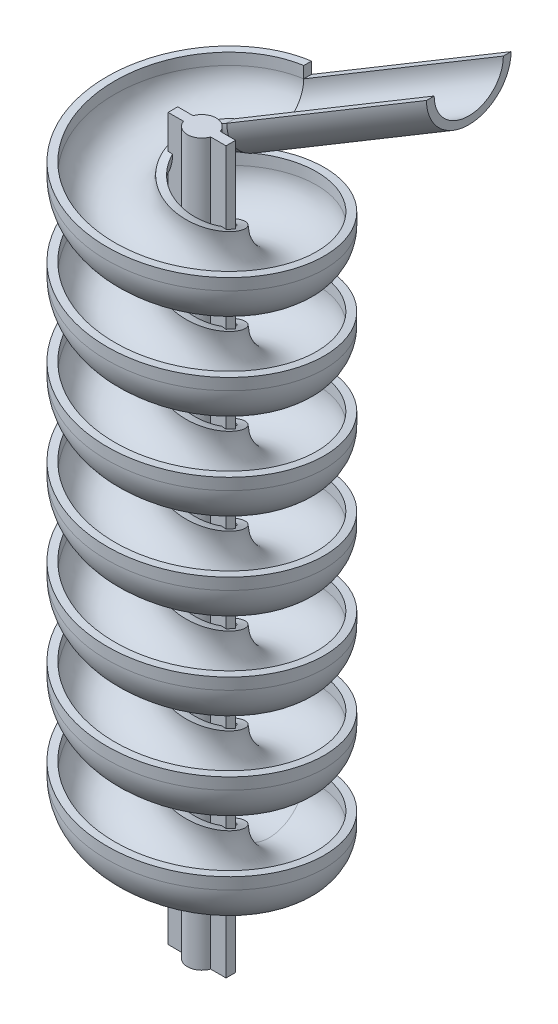
SolidWorks part; units mm, degrees
ref_plane "Front Plane" through (0, 0, 0) normal (0, 0, 1) x (1, 0, 0)
ref_plane "Top Plane" through (0, 0, 0) normal (0, 1, 0) x (1, 0, 0)
ref_plane "Right Plane" through (0, 0, 0) normal (1, 0, 0) x (0, 0, -1)
sketch "Sketch1" plane through (0, 0, 0) normal (0, 1, 0) x (1, 0, 0)
  circle A0 centre (0, 0) radius 35
  dimension "D1" = 70
curve "Helix/Spiral1" pitch 45 height 315 turns 7
sketch "Sketch29" plane through (0, 0, 0) normal (1, 0, 0) x (0, 0, -1)
  line L1 (12.9964, 314.8972) -> (16.9964, 314.8972)
  line L2 (56.9964, 314.8972) -> (56.9964, 320.8972)
  line L3 (56.9964, 320.8972) -> (52.9964, 320.8972)
  line L4 (52.9964, 320.8972) -> (52.9964, 314.8972)
  arc A0 (16.9964, 314.8972) -> (52.9964, 314.8972) centre (34.9964, 314.8972) ccw
  arc A1 (12.9964, 314.8972) -> (56.9964, 314.8972) centre (34.9964, 314.8972) ccw
  spline S0 degree 3 poles (35, 0) (35, 0.5663) (34.3375, 1.7033) (31.412, 3.4052) (26.7194, 5.1082) (20.5238, 6.8108) (13.1735, 8.5135) (5.0821, 10.2162) (-3.2951, 11.9189) (-11.487, 13.6216) (-19.0326, 15.3243) (-25.5076, 17.027) (-30.5477, 18.7297) (-33.8692, 20.4324) (-35.2854, 22.1351) (-34.7166, 23.8378) (-32.1949, 25.5405) (-27.8619, 27.2432) (-21.9616, 28.9459) (-14.8258, 30.6486) (-6.856, 32.3514) (1.4995, 34.0541) (9.7707, 35.7568) (17.4922, 37.4595) (24.2296, 39.1622) (29.604, 40.8649) (33.3131, 42.5676) (35.148, 44.2703) (35.0057, 45.973) (32.8942, 47.6757) (28.9321, 49.3784) (23.3425, 51.0811) (16.4397, 52.7838) (8.6121, 54.4865) (0.3, 56.1892) (-8.029, 57.8919) (-15.9063, 59.5946) (-22.8887, 61.2973) (-28.5836, 63) (-32.6705, 64.7027) (-34.9194, 66.4054) (-35.204, 68.1081) (-33.5081, 69.8108) (-29.9272, 71.5135) (-24.6628, 73.2162) (-18.0109, 74.9189) (-10.3458, 76.6216) (-2.0987, 78.3243) (6.2665, 80.027) (14.2791, 81.7297) (21.4885, 83.4324) (27.489, 85.1351) (31.9431, 86.8378) (34.6002, 88.5405) (35.3109, 90.2432) (34.0351, 91.9459) (30.8447, 93.6486) (25.9191, 95.3514) (19.5354, 97.0541) (12.0527, 98.7568) (3.892, 100.4595) (-4.4877, 102.1622) (-12.6149, 103.8649) (-20.0324, 105.5676) (-26.3231, 107.2703) (-31.1328, 108.973) (-34.1912, 110.6757) (-35.3262, 112.3784) (-34.4738, 114.0811) (-31.6821, 115.7838) (-27.1081, 117.4865) (-21.0091, 119.1892) (-13.7283, 120.8919) (-5.6751, 122.5946) (2.6973, 124.2973) (10.918, 126) (18.5244, 127.7027) (25.0888, 129.4054) (30.2418, 131.1081) (33.6935, 132.8108) (35.2498, 134.5135) (34.8231, 136.2162) (32.4373, 137.9189) (28.2268, 139.6216) (22.4284, 141.3243) (15.3683, 143.027) (7.4436, 144.7297) (-0.8999, 146.4324) (-9.1927, 148.1351) (-16.9684, 149.8378) (-23.7895, 151.5405) (-29.2723, 153.2432) (-33.1084, 154.9459) (-35.0819, 156.6486) (-35.0819, 158.3514) (-33.1084, 160.0541) (-29.2723, 161.7568) (-23.7895, 163.4595) (-16.9684, 165.1622) (-9.1927, 166.8649) (-0.8999, 168.5676) (7.4436, 170.2703) (15.3683, 171.973) (22.4284, 173.6757) (28.2268, 175.3784) (32.4373, 177.0811) (34.8231, 178.7838) (35.2498, 180.4865) (33.6935, 182.1892) (30.2418, 183.8919) (25.0888, 185.5946) (18.5244, 187.2973) (10.918, 189) (2.6973, 190.7027) (-5.6751, 192.4054) (-13.7283, 194.1081) (-21.0091, 195.8108) (-27.1081, 197.5135) (-31.6821, 199.2162) (-34.4738, 200.9189) (-35.3262, 202.6216) (-34.1912, 204.3243) (-31.1328, 206.027) (-26.3231, 207.7297) (-20.0324, 209.4324) (-12.6149, 211.1351) (-4.4877, 212.8378) (3.892, 214.5405) (12.0527, 216.2432) (19.5354, 217.9459) (25.9191, 219.6486) (30.8447, 221.3514) (34.0351, 223.0541) (35.3109, 224.7568) (34.6002, 226.4595) (31.9431, 228.1622) (27.489, 229.8649) (21.4885, 231.5676) (14.2791, 233.2703) (6.2665, 234.973) (-2.0987, 236.6757) (-10.3458, 238.3784) (-18.0109, 240.0811) (-24.6628, 241.7838) (-29.9272, 243.4865) (-33.5081, 245.1892) (-35.204, 246.8919) (-34.9194, 248.5946) (-32.6705, 250.2973) (-28.5836, 252) (-22.8887, 253.7027) (-15.9063, 255.4054) (-8.029, 257.1081) (0.3, 258.8108) (8.6121, 260.5135) (16.4397, 262.2162) (23.3425, 263.9189) (28.9321, 265.6216) (32.8942, 267.3243) (35.0057, 269.027) (35.148, 270.7297) (33.3131, 272.4324) (29.604, 274.1351) (24.2296, 275.8378) (17.4922, 277.5405) (9.7707, 279.2432) (1.4995, 280.9459) (-6.856, 282.6486) (-14.8258, 284.3514) (-21.9616, 286.0541) (-27.8619, 287.7568) (-32.1949, 289.4595) (-34.7166, 291.1622) (-35.2854, 292.8649) (-33.8692, 294.5676) (-30.5477, 296.2703) (-25.5076, 297.973) (-19.0326, 299.6757) (-11.487, 301.3784) (-3.2951, 303.0811) (5.0821, 304.7838) (13.1735, 306.4865) (20.5238, 308.1892) (26.7194, 309.8918) (31.412, 311.5948) (34.3375, 313.2967) (35, 314.4337) (35, 315) knots 0 0 0 0 0.005405 0.010811 0.016216 0.021622 0.027027 0.032432 0.037838 0.043243 0.048649 0.054054 0.059459 0.064865 0.07027 0.075676 0.081081 0.086486 0.091892 0.097297 0.102703 0.108108 0.113514 0.118919 0.124324 0.12973 0.135135 0.140541 0.145946 0.151351 0.156757 0.162162 0.167568 0.172973 0.178378 0.183784 0.189189 0.194595 0.2 0.205405 0.210811 0.216216 0.221622 0.227027 0.232432 0.237838 0.243243 0.248649 0.254054 0.259459 0.264865 0.27027 0.275676 0.281081 0.286486 0.291892 0.297297 0.302703 0.308108 0.313514 0.318919 0.324324 0.32973 0.335135 0.340541 0.345946 0.351351 0.356757 0.362162 0.367568 0.372973 0.378378 0.383784 0.389189 0.394595 0.4 0.405405 0.410811 0.416216 0.421622 0.427027 0.432432 0.437838 0.443243 0.448649 0.454054 0.459459 0.464865 0.47027 0.475676 0.481081 0.486486 0.491892 0.497297 0.502703 0.508108 0.513514 0.518919 0.524324 0.52973 0.535135 0.540541 0.545946 0.551351 0.556757 0.562162 0.567568 0.572973 0.578378 0.583784 0.589189 0.594595 0.6 0.605405 0.610811 0.616216 0.621622 0.627027 0.632432 0.637838 0.643243 0.648649 0.654054 0.659459 0.664865 0.67027 0.675676 0.681081 0.686486 0.691892 0.697297 0.702703 0.708108 0.713514 0.718919 0.724324 0.72973 0.735135 0.740541 0.745946 0.751351 0.756757 0.762162 0.767568 0.772973 0.778378 0.783784 0.789189 0.794595 0.8 0.805405 0.810811 0.816216 0.821622 0.827027 0.832432 0.837838 0.843243 0.848649 0.854054 0.859459 0.864865 0.87027 0.875676 0.881081 0.886486 0.891892 0.897297 0.902703 0.908108 0.913514 0.918919 0.924324 0.92973 0.935135 0.940541 0.945946 0.951351 0.956757 0.962162 0.967568 0.972973 0.978378 0.983784 0.989189 0.994595 1 1 1 1 construction
  dimension "D1" = 22
  dimension "D2" = 18
  dimension "D3" = 6
sweep "Sweep2" add profiles "Sketch29" path "Helix/Spiral1"
sketch "Sketch24" plane through (0, 0, 0) normal (1, 0, 0) x (0, 0, -1)
  line L0 (56.9964, 320.8972) -> (56.9964, 314.8972) construction
  line L2 (52.9964, 320.8972) -> (52.9964, 314.8972)
  line L3 (16.9964, 314.8972) -> (12.9964, 314.8972)
  line L5 (16.9964, 314.8972) -> (12.9964, 314.8972)
  line L9 (56.9964, 320.8972) -> (52.9964, 320.8972)
  line L10 (56.9964, 314.8972) -> (52.9964, 314.8972)
  line L11 (56.9964, 314.8972) -> (56.9964, 320.8972)
  arc A2 (12.9964, 314.8972) -> (56.9964, 314.8972) centre (34.9964, 314.8972) ccw
  arc A3 (16.9964, 314.8972) -> (52.9964, 314.8972) centre (34.9964, 314.8972) ccw
  arc A4 (12.9964, 314.8972) -> (56.9964, 314.8972) centre (34.9964, 314.8972) ccw
  arc A6 (16.9964, 314.8972) -> (52.9964, 314.8972) centre (34.9964, 314.8972) ccw
  dimension "D1" = 0
sketch "Sketch30" plane through (0, 0, 0) normal (0, 1, 0) x (1, 0, 0)
  line L0 (-15.0711, -2.5) -> (-15.0711, 2.5)
  line L1 (-15.0711, 2.5) -> (-7.0711, 2.5)
  line L2 (-15.0711, -2.5) -> (-7.0711, -2.5)
  line L3 (7.0711, 2.5) -> (15.0711, 2.5)
  line L4 (15.0711, 2.5) -> (15.0711, -2.5)
  line L5 (15.0711, -2.5) -> (7.0711, -2.5)
  arc A0 (-7.0711, -2.5) -> (7.0711, -2.5) centre (0, 0) ccw
  arc A1 (7.0711, 2.5) -> (-7.0711, 2.5) centre (0, 0) ccw
  dimension "D1" = 15
  dimension "D2" = 5
  dimension "D3" = 8
extrude "Boss-Extrude1" add sketch "Sketch30" along normal blind 320 and the other way blind 55
ref_plane "Plane5" through (61.8711, 0, 0) normal (-1, 0, 0) x (0, 0, 1)
sketch "Sketch31" plane through (61.8711, 0, 0) normal (-1, 0, 0) x (0, 0, 1)
  line L0 (-77, 385.1789) -> (-77, 287.7651) construction
  line L1 (-99, 335.0992) -> (-95, 335.0992)
  line L2 (-59, 335.0992) -> (-55, 335.0992)
  arc A0 (-99, 407.1789) -> (-55, 407.1789) centre (-77, 407.1789) ccw construction
  arc A1 (-55, 335.0992) -> (-99, 335.0992) centre (-77, 335.0992) cw
  arc A2 (-59, 335.0992) -> (-95, 335.0992) centre (-77, 335.0992) cw
  dimension "D1" = 18
  dimension "D2" = 22
loft "Loft1" add profiles "Sketch31", "Sketch24"
ref_plane "Plane6" through (-57.5751, 0, 0) normal (1, 0, 0) x (0, 0, -1)
sketch "Sketch33" plane through (0, 0, 0) normal (-1, 0, 0) x (0, 0, 1)
  line L4 (-52.9964, 5.8972) -> (-56.9964, 5.8972)
  line L5 (-56.9964, 5.8972) -> (-56.9964, -0.1028)
  line L6 (-12.9964, -0.1028) -> (-16.9964, -0.1028)
  line L7 (-52.9964, -0.1028) -> (-52.9964, 5.8972)
  line L8 (-52.9964, -0.1028) -> (-56.9964, -0.1028)
  line L10 (-12.9964, -0.1028) -> (-16.9964, -0.1028)
  arc A2 (-56.9964, -0.1028) -> (-12.9964, -0.1028) centre (-34.9964, -0.1028) ccw
  arc A3 (-52.9964, -0.1028) -> (-16.9964, -0.1028) centre (-34.9964, -0.1028) ccw
  arc A4 (-56.9964, -0.1028) -> (-12.9964, -0.1028) centre (-34.9964, -0.1028) ccw
  arc A5 (-52.9964, -0.1028) -> (-16.9964, -0.1028) centre (-34.9964, -0.1028) ccw
  dimension "D1" = 0
sketch "Sketch32" plane through (-57.5751, 0, 0) normal (1, 0, 0) x (0, 0, -1)
  line L0 (64.4454, -11.5601) -> (60.4454, -11.5601)
  line L1 (24.4454, -11.5601) -> (20.4454, -11.5601)
  line L2 (42.4454, -20.8221) -> (42.4454, -66.2008) construction
  line L3 (20.4454, -11.5601) -> (64.4454, -11.5601) construction
  arc A0 (64.4454, -11.5601) -> (20.4454, -11.5601) centre (42.4454, -11.5601) cw
  arc A1 (60.4454, -11.5601) -> (24.4454, -11.5601) centre (42.4454, -11.5601) cw
  dimension "D1" = 22
  dimension "D2" = 18
loft "Loft2" add profiles "Sketch32", "Sketch33"
